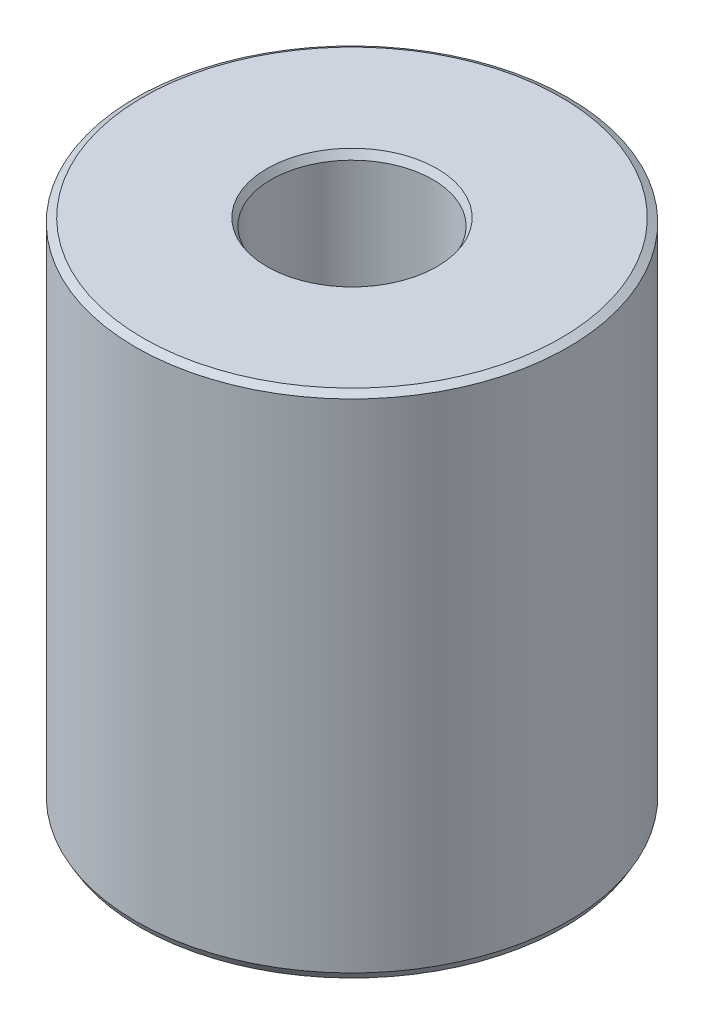
SolidWorks part; units mm, degrees
ref_plane "Front Plane" through (0, 0, 0) normal (0, 0, 1) x (1, 0, 0)
ref_plane "Top Plane" through (0, 0, 0) normal (0, 1, 0) x (1, 0, 0)
ref_plane "Right Plane" through (0, 0, 0) normal (1, 0, 0) x (0, 0, -1)
sketch "Sketch1" plane through (0, 0, 0) normal (0, 1, 0) x (1, 0, 0)
  circle A0 centre (0, 0) radius 22.5
  dimension "SLEEVE_OD" = 45
extrude "Boss-Extrude1" add sketch "Sketch1" along normal blind 52.94
sketch "Sketch2" plane through (0, 0, 0) normal (0, 1, 0) x (1, 0, 0)
  circle A0 centre (0, 0) radius 8.4038
  dimension "BORE_D" = 16.8075
extrude "Cut-Extrude1" cut sketch "Sketch2" along normal through all
chamfer "Chamfer1" distance 0.4421 angle 60 4 edges at (0, 52.94, 8.4038) (0, 0, 8.4038) (0, 0, 22.5) (0, 52.94, 22.5) first distance on face at (0, 52.94, 8.4038) first distance on face at (0, 0, 8.4038) first distance on face at (0, 52.94, 22.5)
